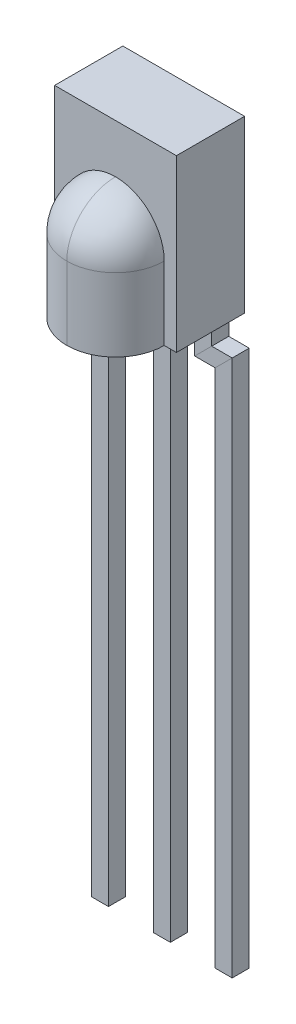
SolidWorks part; units mm, degrees
ref_plane "Ön Düzlem" through (0, 0, 0) normal (0, 0, 1) x (1, 0, 0)
ref_plane "Üst Düzlem" through (0, 0, 0) normal (0, 1, 0) x (1, 0, 0)
ref_plane "Sağ Düzlem" through (0, 0, 0) normal (1, 0, 0) x (0, 0, -1)
sketch "Çizim1" plane through (0, 0, 0) normal (0, 0, 1) x (1, 0, 0)
  line L1 (0, 0) -> (5, 0)
  line L2 (0, 0) -> (0, 7)
  line L3 (0, 7) -> (5, 7)
  line L4 (5, 0) -> (5, 7)
  dimension "D1" = 5
  dimension "D2" = 7
extrude "Yükseklik-Ekstrüzyon1" add sketch "Çizim1" along normal blind 2.8
sketch "Çizim2" plane through (0, 0, 2.8) normal (0, 0, 1) x (1, 0, 0)
  line L0 (0, 0) -> (5, 0) construction
  line L1 (0.5, 0) -> (4.5, 0)
  line L2 (0.5, 0) -> (0.5, 5)
  line L3 (0.5, 5) -> (4.5, 5)
  line L4 (4.5, 0) -> (4.5, 5)
  line L5 (0, 7) -> (0, 0) construction
  dimension "D1" = 4
  dimension "D2" = 0.5
  dimension "D3" = 5
extrude "Yükseklik-Ekstrüzyon2" add sketch "Çizim2" along normal blind 2
fillet "Radyus2" radius 2 5 edges at (2.5, 5, 4.8) (4.5, 5, 3.8) (0.5, 5, 3.8) (4.5, 2.5, 4.8) (0.5, 2.5, 4.8)
sketch "Çizim3" plane through (0, 0, 0) normal (0, -1, 0) x (1, 0, 0)
  line L9 (3.85, 0.9) -> (4.55, 0.9)
  line L10 (3.85, 0.9) -> (3.85, 0.2)
  line L11 (3.85, 0.2) -> (4.55, 0.2)
  line L12 (4.55, 0.9) -> (4.55, 0.2)
ref_plane "Düzlem1" through (0, 0, 0.55) normal (0, 0, -1) x (-1, 0, 0)
sketch "Çizim4" plane through (0, 0, 0.55) normal (0, 0, -1) x (-1, 0, 0)
  line L0 (-4.2, 0) -> (-4.2, -1.3)
  line L1 (-3.85, 0) -> (-4.55, 0) construction
  line L2 (-4.2, -1.3) -> (-5.04, -1.3)
  line L3 (-5.04, -1.3) -> (-5.04, -23)
  line L9 (-5, 7) -> (0, 7) construction
  point P17 (-2.5, -23)
  dimension "D1" = 1.3
  dimension "D5" = 30
sweep "Süpür1" add profiles "Çizim3" path "Çizim4"
ref_plane "Düzlem2" through (2.5, 0, 0) normal (1, 0, 0) x (0, 0, -1)
mirror "Aynalama1" about plane through (2.5, 0, 0) normal (1, 0, 0) of "Süpür1"
sketch "Çizim5" plane through (0, 0, 0) normal (0, -1, 0) x (1, 0, 0)
  line L0 (0, 0) -> (5, 0) construction
  line L1 (2.85, 0.2) -> (2.15, 0.2)
  line L2 (2.85, 0.2) -> (2.85, 0.9)
  line L3 (2.85, 0.9) -> (2.15, 0.9)
  line L4 (2.15, 0.2) -> (2.15, 0.9)
  line L5 (3.85, 0.2) -> (3.85, 0.9) construction
  dimension "D1" = 0.7
  dimension "D2" = 0.7
  dimension "D3" = 0.2
  dimension "D4" = 1
sketch "Çizim6" plane through (0, 0, 0.55) normal (0, 0, -1) x (-1, 0, 0)
  line L0 (-2.5, 0) -> (-2.5, -23.0027)
  line L1 (-2.85, 0) -> (-2.15, 0) construction
sweep "Süpür2" add profiles "Çizim5" path "Çizim6"
